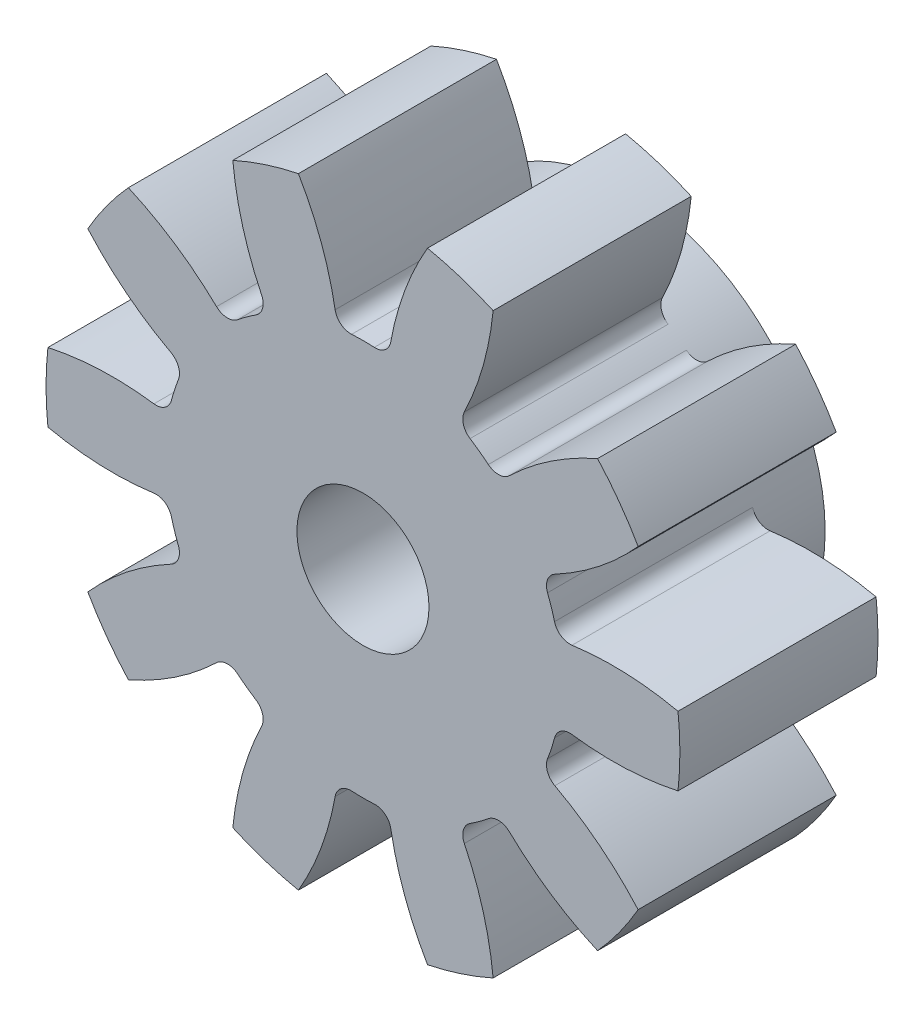
SolidWorks part; units mm, degrees
ref_plane "Front Plane" through (0, 0, 0) normal (0, 0, 1) x (1, 0, 0)
ref_plane "Top Plane" through (0, 0, 0) normal (0, 1, 0) x (1, 0, 0)
ref_plane "Right Plane" through (0, 0, 0) normal (1, 0, 0) x (0, 0, -1)
sketch "Sketch1" plane through (0, 0, 0) normal (0, 0, 1) x (1, 0, 0)
  circle A0 centre (0, 0) radius 10
  circle A1 centre (0, 0) radius 12
  circle A2 centre (0, 0) radius 7.5
  dimension "D1" = 20
  dimension "D2" = 24
  dimension "D3" = 4.5
extrude "Boss-Extrude1" add sketch "Sketch1" along normal mid plane 425 contours A1
sketch "Sketch2" plane through (0, 0, 0) normal (0, 0, 1) x (1, 0, 0)
  line L0 (0, 0) -> (0, 12) construction
  line L1 (-1.5643, 9.8769) -> (1.5643, 9.8769) construction
  line L2 (-0.9691, 7.4371) -> (0, 0) construction
  line L3 (0, 5.5789) -> (-2.6051, 12.7363) construction
  line L4 (0, 0) -> (3.7082, 11.4127) construction
  line L5 (1.5643, 9.8769) -> (4.5399, 8.9101) construction
  circle A0 centre (0, 0) radius 12 construction
  arc A1 (-3.0254, 12.6431) -> (-0.9691, 7.4371) centre (-12.3373, 5.9558) cw
  arc A2 (3.0254, 12.6431) -> (0.9691, 7.4371) centre (12.3373, 5.9558) ccw
  circle A3 centre (0, 0) radius 7.5 construction
  arc A4 (0.9691, 7.4371) -> (-0.9691, 7.4371) centre (0, 0) ccw
  circle A5 centre (0, 0) radius 12 construction
  circle A6 centre (0, 0) radius 10 construction
  circle A7 centre (0, 0) radius 13
  arc A8 (3.0254, 12.6431) -> (-3.0254, 12.6431) centre (0, 0) ccw
  dimension "D2" = 1.9081
  dimension "D3" = 20
  dimension "D4" = 18
extrude "Cut-Extrude1" cut sketch "Sketch2" against normal through all both and the other way through all
fillet "Fillet1" radius 0.6 1 edges at (-0.9691, 7.4371, 0) type face fillet first side face at (-1.5984, 9.6298, 0) second side face at (0, 7.4686, 0)
fillet "Fillet2" radius 0.6 1 edges at (0.9691, 7.4371, 0) type face fillet first side face at (1.5984, 9.6298, 0) second side face at (0.2709, 7.4788, 0)
sketch "Sketch3" plane through (0, 0, -212.5) normal (0, 0, -1) x (-1, 0, 0)
pattern_circular "CirPattern2" count 10 over 360 about axis through (0, 0, 212.5) along (0, 0, 1) of "Cut-Extrude1", "Fillet1", "Fillet2"
sketch "Sketch4" plane through (0, 0, -212.5) normal (0, 0, -1) x (-1, 0, 0)
  circle A0 centre (0, 0) radius 7.5
  circle A1 centre (0, 0) radius 2.5
  dimension "D1" = 5
extrude "Boss-Extrude2" add sketch "Sketch4" along normal mid plane 5 contours A0 | A1
sketch "Sketch5" plane through (0, 0, -212.5) normal (0, 0, -1) x (-1, 0, 0)
  circle A0 centre (0, 0) radius 3
extrude "Cut-Extrude2" cut sketch "Sketch5" against normal blind 32 and the other way through all
sketch "Sketch6" plane through (0, 0, 212.5) normal (0, 0, 1) x (1, 0, 0)
  circle A0 centre (0, 0) radius 7.5
  dimension "D1" = 15
extrude "Boss-Extrude3" add sketch "Sketch6" along normal mid plane 12
ref_plane "Plane1" through (0, 0, -205) normal (0, 0, -1) x (-1, 0, 0)
sketch "Sketch7" plane through (0, 0, 218.5) normal (0, 0, 1) x (1, 0, 0)
  circle A0 centre (0, 0) radius 12
extrude "Cut-Extrude3" cut sketch "Sketch7" against normal up to surface (423.5 mm away) contours A0 up to plane "Plane1"
sketch "Sketch8" plane through (0, 0, -215) normal (0, 0, -1) x (-1, 0, 0)
  circle A0 centre (0, 0) radius 1.65
  circle A1 centre (0, 0) radius 7.5
  dimension "D1" = 3.3
extrude "Boss-Extrude4" add sketch "Sketch8" against normal up to surface (10 mm away) up to face at (-3, 0, -205)
sketch "Sketch9" plane through (0, 0, -192.6026) normal (0, 0, 1) x (1, 0, 0)
  circle A0 centre (0, 0) radius 2.5
  dimension "D1" = 5
extrude "Cut-Extrude4" cut sketch "Sketch9" against normal through all contours A0
equation "\"Module\"= 2mm"
equation "\"Number of Teeth\"= 10"
equation "\"D1@Sketch1\"=\"Module\" * \"Number of Teeth\""
equation "\"D2@Sketch1\"=(\"Number of Teeth\" + 2) * \"Module\""
equation "\"D3@Sketch1\"=\"Module\" * if( \"Module\" = > 1.25, 2.25, 2.4)"
equation "\"D4@Sketch2\"=180 / \"Number of Teeth\""
equation "\"D1@Fillet1\"=0.3 * \"Module\""
